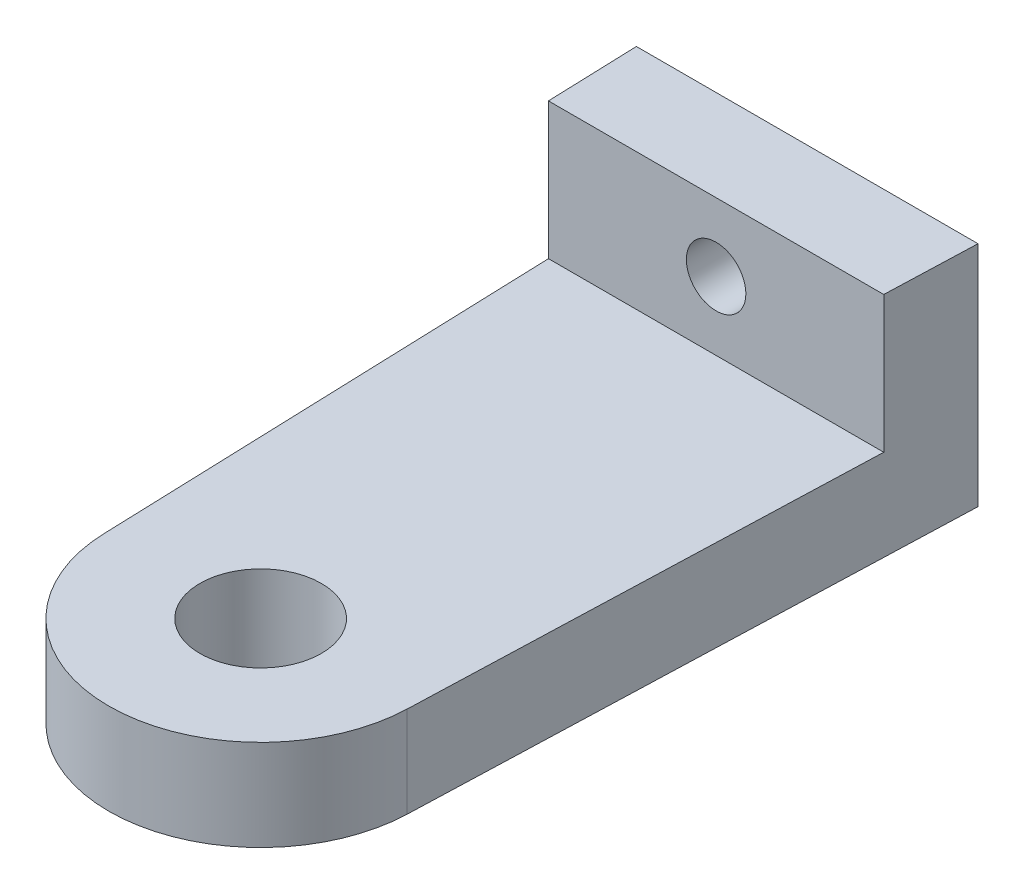
SolidWorks part; units mm, degrees
ref_plane "Front Plane" through (0, 0, 0) normal (1, 0, 0) x (0, 1, 0)
ref_plane "Top Plane" through (0, 0, 0) normal (0, 0, 1) x (0, 1, 0)
ref_plane "Right Plane" through (0, 0, 0) normal (0, 1, 0) x (-1, 0, 0)
sketch "Sketch2" plane through (0, 0, 0) normal (0, 1, 0) x (-1, 0, 0)
  line L0 (-14.2875, 0) -> (14.2875, 0)
  line L1 (-14.2875, 0) -> (-12.6924, 46.1586)
  line L2 (12.6924, 46.1586) -> (14.2875, 0)
  line L3 (0, 58.42) -> (0, 0) construction
  line L4 (-14.0242, 7.62) -> (14.0242, 7.62)
  circle A0 centre (0, 45.72) radius 5.08
  arc A1 (12.6924, 46.1586) -> (-12.6924, 46.1586) centre (0, 45.72) ccw
  circle A2 centre (0, 45.72) radius 12.7 construction
  point P7 (0, 0)
  dimension "D4" = 10.16
  dimension "D2" = 58.42
  dimension "D3" = 28.575
  dimension "D5" = 7.62
  dimension "D1" = 7.62
extrude "Boss-Extrude2" add sketch "Sketch2" along normal mid plane 7.62 contours L3 A1 L1 L0 | A1 L3 L0 L2 | A1 L3 A0 | L3 A1 A0 region at (0, 0, 3.7982) region at (0, 0, 30.3055)
extrude "Boss-Extrude4" add sketch "Sketch2<4>" along normal blind 15.24 contours L4 L1 L0 L2 region at (0, 0, 3.7982)
sketch "Sketch2<4>" plane through (0, 0, 0) normal (0, 1, 0) x (-1, 0, 0) same geometry as "Sketch2"
hole_wizard "#9 (0.196) Diameter Hole1" positions "Sketch6" profile "Sketch8" hole size "#9" standard "ANSI Inch" end condition through all
sketch "Sketch6" plane through (0, 0, 7.62) normal (0, 0, 1) x (1, 0, 0)
  line L1 (-14.0242, 15.24) -> (14.0242, 3.81) construction
  point P0 (0, 9.525)
  point P21 (0, 0)
  point P22 (0, 9.525)
sketch "Sketch8" plane through (0, 9.525, 7.62) normal (1, 0, 0) x (0, -1, 0)
  line L0 (0, 0) -> (0, 7.62)
  line L1 (0, 7.62) -> (2.4892, 7.62)
  line L2 (2.4892, 7.62) -> (2.4892, 0)
  line L5 (2.4892, 0) -> (0, 0)
  line L11 (0, -6.35) -> (0, 107.95) construction
  dimension "Thru Hole Dia." = 4.9784
  dimension "Thru Hole Depth" = 7.62
